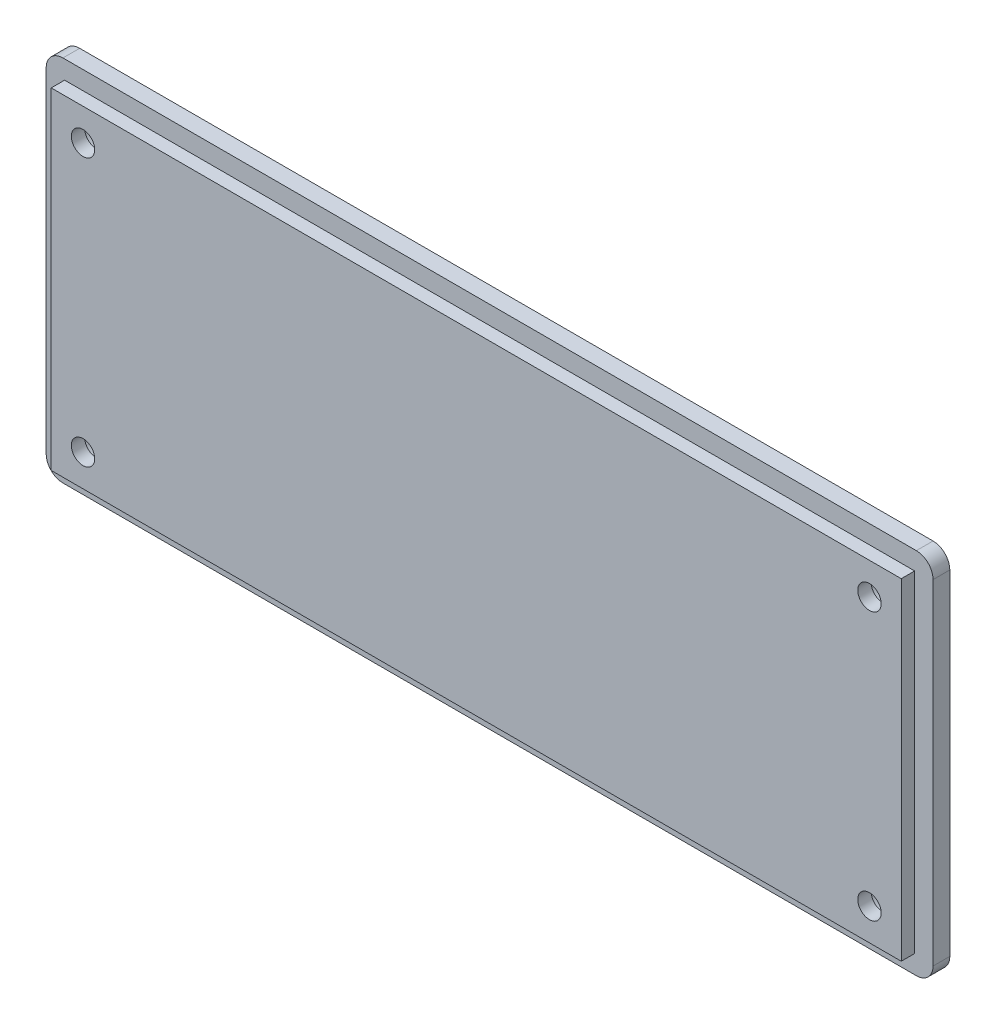
SolidWorks part; units mm, degrees
material "ABS"
ref_plane "Спереди" through (0, 0, 0) normal (0, 0, 1) x (1, 0, 0)
ref_plane "Сверху" through (0, 0, 0) normal (0, 1, 0) x (1, 0, 0)
ref_plane "Справа" through (0, 0, 0) normal (1, 0, 0) x (0, 0, -1)
sketch "Эскиз1" plane through (0, 0, 0) normal (0, 0, 1) x (1, 0, 0)
  line L1 (-53, -22) -> (53, -22)
  line L2 (-53, -22) -> (-53, 22)
  line L3 (-53, 22) -> (53, 22)
  line L4 (53, -22) -> (53, 22)
  line L5 (-53, -22) -> (53, 22) construction
  line L6 (-53, 22) -> (53, -22) construction
  point P0 (0, 0)
  dimension "D1" = 106
  dimension "D2" = 44
extrude "Body" add sketch "Эскиз1" along normal blind 2
sketch "Эскиз2" plane through (0, 0, 2) normal (0, 0, 1) x (1, 0, 0)
  line L0 (-53, 22) -> (-53, -22) construction
  line L1 (-50.8, -19.8) -> (50.8, -19.8)
  line L2 (-50.8, -19.8) -> (-50.8, 19.8)
  line L3 (-50.8, 19.8) -> (50.8, 19.8)
  line L4 (50.8, -19.8) -> (50.8, 19.8)
  line L5 (-50.8, -19.8) -> (50.8, 19.8) construction
  line L6 (-50.8, 19.8) -> (50.8, -19.8) construction
  line L7 (53, 22) -> (-53, 22) construction
  point P0 (0, 0)
  dimension "D1" = 2.2
  dimension "D2" = 2.2
extrude "InternalBody" add sketch "Эскиз2" along normal blind 1.6
sketch "Эскиз3" plane through (0, 0, 0) normal (0, 0, -1) x (-1, 0, 0)
  line L0 (53, -22) -> (-53, -22) construction
  line L1 (51, -20) -> (43, -20) construction
  line L2 (51, -20) -> (51, -12) construction
  line L3 (51, -12) -> (43, -12) construction
  line L4 (43, -20) -> (43, -12) construction
  line L5 (51, -20) -> (43, -12) construction
  line L6 (51, -12) -> (43, -20) construction
  line L7 (53, 22) -> (53, -22) construction
  circle A0 centre (47, -16) radius 1.4
  circle A1 centre (47, -16) radius 2.5
  point P0 (47, -16)
  dimension "D4" = 2.8
  dimension "D5" = 5
  dimension "D1" = 2
  dimension "D2" = 2
  dimension "D3" = 8
extrude "HoleScrew" cut sketch "Эскиз3" against normal through all contours A0 region at (-47, -16, 0)
extrude "TopScrewPlace" cut sketch "Эскиз3<3>" against normal blind 2 contours A1 A0 region at (-44.5707, -16, 0)
sketch "Эскиз3<3>" plane through (0, 0, 0) normal (0, 0, -1) x (-1, 0, 0) same geometry as "Эскиз3"
mirror "ScrewMrror1" about plane through (0, 0, 0) normal (0, 1, 0) of "TopScrewPlace", "HoleScrew"
mirror "ScrewMirror2" about plane through (0, 0, 0) normal (1, 0, 0) of "ScrewMrror1", "TopScrewPlace"
fillet "Corners" radius 2 4 edges at (-53, -22, 1) (53, -22, 1) (53, 22, 1) (-53, 22, 1)
